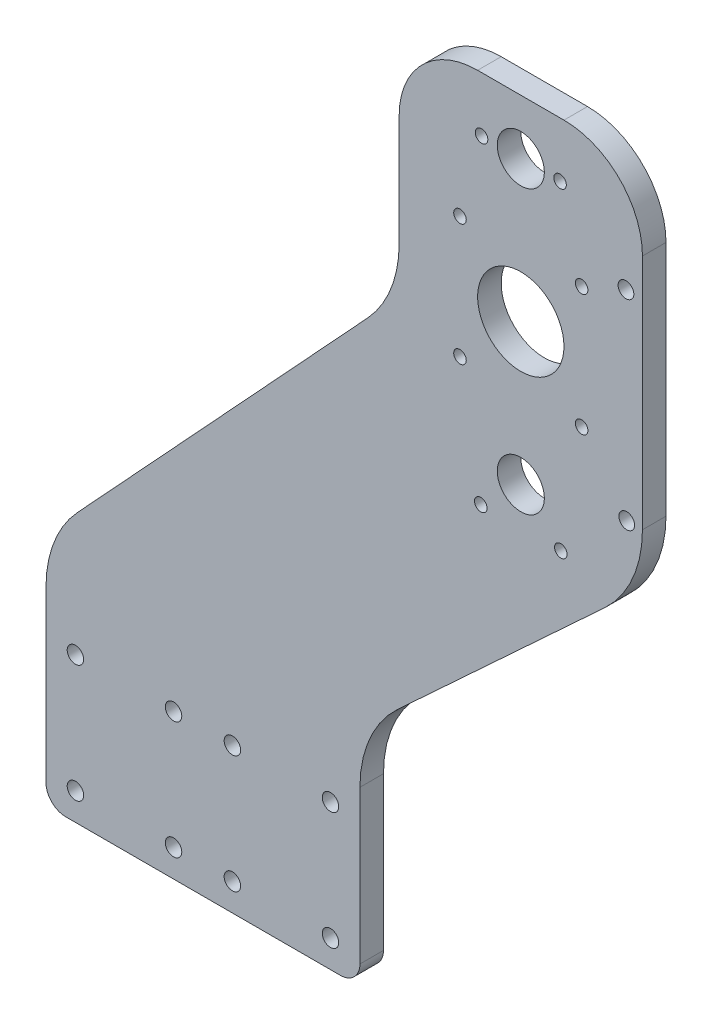
SolidWorks part; units mm, degrees
ref_plane "Front Plane" through (0, 0, 0) normal (0, 0, 1) x (1, 0, 0)
ref_plane "Top Plane" through (0, 0, 0) normal (0, 1, 0) x (1, 0, 0)
ref_plane "Right Plane" through (0, 0, 0) normal (1, 0, 0) x (0, 0, -1)
sketch "Sketch1" plane through (0, 0, 0) normal (0, 0, 1) x (1, 0, 0)
  line L0 (-23.4503, -99.2073) -> (-23.4503, -15.4242) construction
  line L1 (-58.4503, -99.2073) -> (11.5497, -99.2073)
  line L2 (-63.4503, -94.2073) -> (-63.4503, -50.959)
  line L3 (-63.4503, -94.2073) -> (-23.4503, -94.2073) construction
  line L4 (16.5497, -94.2073) -> (16.5497, -55.2061)
  line L5 (46.5497, 118.0426) -> (68.5497, 118.0426)
  line L6 (26.5497, 98.0426) -> (26.5497, 69.7942)
  line L7 (57.5497, 118.0426) -> (57.5497, 32.1026) construction
  line L8 (88.5497, 98.0426) -> (88.5497, 37.6266)
  line L9 (-43.4503, -77.2073) -> (-43.4503, -94.2073) construction
  line L10 (-55.9503, -62.2073) -> (-30.9503, -62.2073) construction
  line L11 (18.5677, 49.4176) -> (-55.4683, -30.5824)
  line L12 (78.9209, 15.6036) -> (26.1784, -33.1831)
  line L13 (-55.9503, -62.2073) -> (-55.9503, -92.2073) construction
  line L14 (-55.9503, -92.2073) -> (-30.9503, -92.2073) construction
  line L15 (-30.9503, -62.2073) -> (-30.9503, -92.2073) construction
  line L16 (-55.9503, -62.2073) -> (-30.9503, -92.2073) construction
  line L17 (-55.9503, -92.2073) -> (-30.9503, -62.2073) construction
  line L18 (57.5497, 104.0426) -> (57.5497, 32.1026) construction
  line L20 (42.0497, 52.5726) -> (73.0497, 52.5726) construction
  line L21 (42.0497, 52.5726) -> (42.0497, 83.5726) construction
  line L22 (42.0497, 83.5726) -> (73.0497, 83.5726) construction
  line L23 (73.0497, 52.5726) -> (73.0497, 83.5726) construction
  line L24 (42.0497, 52.5726) -> (73.0497, 83.5726) construction
  line L25 (42.0497, 83.5726) -> (73.0497, 52.5726) construction
  arc A0 (78.9209, 15.6036) -> (88.5497, 37.6266) centre (58.5497, 37.6266) ccw
  arc A1 (18.5677, 49.4176) -> (26.5497, 69.7942) centre (-3.4503, 69.7942) ccw
  arc A2 (16.5497, -55.2061) -> (26.1784, -33.1831) centre (46.5497, -55.2061) cw
  arc A3 (-63.4503, -50.959) -> (-55.4683, -30.5824) centre (-33.4503, -50.959) cw
  arc A4 (88.5497, 98.0426) -> (68.5497, 118.0426) centre (68.5497, 98.0426) ccw
  arc A5 (46.5497, 118.0426) -> (26.5497, 98.0426) centre (46.5497, 98.0426) ccw
  arc A6 (16.5497, -94.2073) -> (11.5497, -99.2073) centre (11.5497, -94.2073) cw
  arc A7 (-58.4503, -99.2073) -> (-63.4503, -94.2073) centre (-58.4503, -94.2073) cw
  circle A8 centre (-55.9503, -62.2073) radius 2.1
  circle A9 centre (-30.9503, -62.2073) radius 2.1
  circle A10 centre (-30.9503, -92.2073) radius 2.1
  circle A11 centre (-55.9503, -92.2073) radius 2.1
  circle A12 centre (9.0497, -92.2073) radius 2.1
  circle A13 centre (-15.9503, -92.2073) radius 2.1
  circle A14 centre (-15.9503, -62.2073) radius 2.1
  circle A15 centre (9.0497, -62.2073) radius 2.1
  circle A16 centre (57.5497, 104.0426) radius 6
  circle A17 centre (57.5497, 32.1026) radius 6
  circle A18 centre (57.5497, 68.0726) radius 11
  circle A19 centre (42.0497, 83.5726) radius 1.6
  circle A20 centre (73.0497, 83.5726) radius 1.6
  circle A21 centre (73.0497, 52.5726) radius 1.6
  circle A22 centre (42.0497, 52.5726) radius 1.6
  circle A23 centre (84.5497, 37.6266) radius 2
  circle A24 centre (84.3518, 88.5185) radius 2
  circle A25 centre (47.5497, 104.0426) radius 1.6
  circle A26 centre (47.3518, 22.5785) radius 1.6
  circle A27 centre (67.5497, 104.0426) radius 1.6
  circle A28 centre (67.7476, 22.5785) radius 1.6
  point P0 (0, 0)
  point P1 (57.5497, 82.2289)
  point P15 (26.5497, 58.0426)
  point P20 (-63.4503, -39.2073)
  point P23 (88.5497, 118.0426)
  point P26 (26.5497, 118.0426)
  point P29 (16.5497, -99.2073)
  point P32 (-63.4503, -99.2073)
  point P35 (-43.4503, -77.2073)
  dimension "D5" = 30
  dimension "D6" = 20
  dimension "D7" = 5
  dimension "D14" = 71.94
  dimension "D12" = 31
  dimension "D17" = 4
  dimension "D18" = 10
  dimension "D1" = 80
  dimension "D2" = 22
  dimension "D3" = 90
  dimension "D4" = 60
  dimension "D8" = 25
  dimension "D9" = 60
  dimension "D10" = 22
  dimension "D11" = 80
  dimension "D13" = 30
  dimension "D15" = 14
  dimension "D16" = 31
extrude "Boss-Extrude1" add sketch "Sketch1" along normal blind 6
